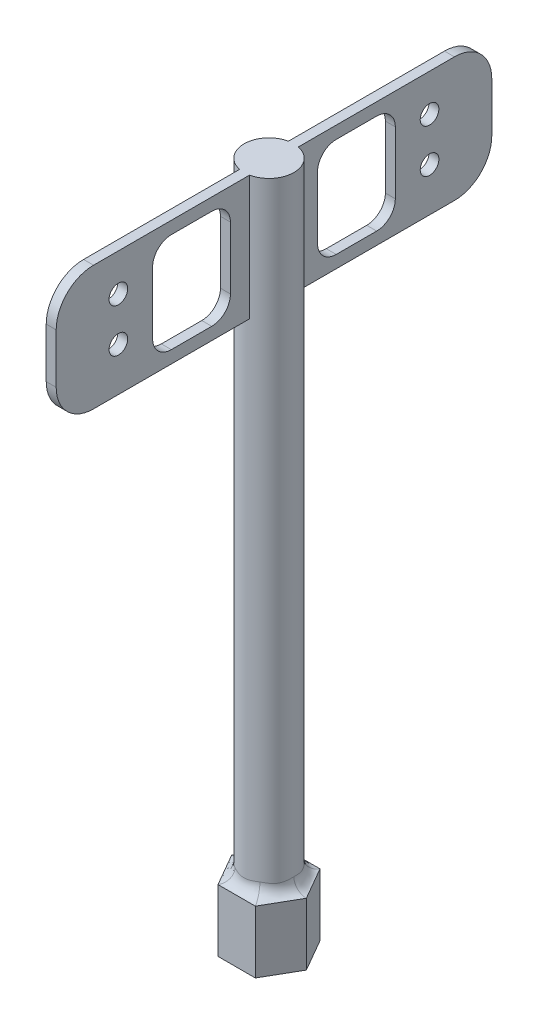
SolidWorks part; units mm, degrees
ref_plane "Front Plane" through (0, 0, 0) normal (0, 0, 1) x (1, 0, 0)
ref_plane "Top Plane" through (0, 0, 0) normal (0, 1, 0) x (1, 0, 0)
ref_plane "Right Plane" through (0, 0, 0) normal (1, 0, 0) x (0, 0, -1)
sketch "Sketch1" plane through (0, 0, 0) normal (0, 1, 0) x (1, 0, 0)
  line L1 (6, 0) -> (3, 5.1962)
  line L2 (3, 5.1962) -> (-3, 5.1962)
  line L3 (-3, 5.1962) -> (-6, 0)
  line L4 (-6, 0) -> (-3, -5.1962)
  line L5 (-3, -5.1962) -> (3, -5.1962)
  line L6 (3, -5.1962) -> (6, 0)
  circle A0 centre (0, 0) radius 5.1962 construction
  dimension "D1" = 6
extrude "Boss-Extrude1" add sketch "Sketch1" along normal blind 10
sketch "Sketch2" plane through (0, 10, 0) normal (0, 1, 0) x (1, 0, 0)
  circle A0 centre (0, 0) radius 4
extrude "Boss-Extrude2" add sketch "Sketch2" along normal blind 100
fillet "Fillet1" radius 2 1 edges at (0, 10, 4)
sketch "Sketch3" plane through (0, 0, 0) normal (0, -1, 0) x (-1, 0, 0)
  circle A0 centre (0, 0) radius 3
extrude "Cut-Extrude1" cut sketch "Sketch3" against normal blind 8
sketch "Sketch4" plane through (0, 110, 0) normal (0, 1, 0) x (1, 0, 0)
  line L1 (-0.8, -35) -> (0.8, -35)
  line L2 (-0.8, -35) -> (-0.8, 35)
  line L3 (-0.8, 35) -> (0.8, 35)
  line L4 (0.8, -35) -> (0.8, 35)
  line L5 (-0.8, -35) -> (0.8, 35) construction
  line L6 (-0.8, 35) -> (0.8, -35) construction
  point P0 (0, 0)
  dimension "D1" = 1.6
  dimension "D2" = 70
extrude "Boss-Extrude3" add sketch "Sketch4" against normal blind 20
sketch "Sketch5" plane through (-0.8, 0, 0) normal (-1, 0, 0) x (0, 0, 1)
  line L0 (0, 0) -> (0, 127.2125) construction
  line L1 (-35, 110) -> (-3.9192, 110) construction
  line L2 (-3.9192, 90) -> (-35, 90) construction
  line L3 (-7, 108) -> (-19.5, 108)
  line L4 (-7, 108) -> (-7, 92)
  line L5 (-7, 92) -> (-19.5, 92)
  line L6 (-19.5, 108) -> (-19.5, 92)
  line L7 (-7, 108) -> (-19.5, 92) construction
  line L8 (-7, 92) -> (-19.5, 108) construction
  line L9 (7, 92) -> (19.5, 92)
  line L10 (7, 108) -> (7, 92)
  line L11 (7, 108) -> (19.5, 108)
  line L12 (19.5, 108) -> (19.5, 92)
  circle A0 centre (-25, 104) radius 1.5
  circle A1 centre (-25, 97) radius 1.5
  circle A2 centre (25, 97) radius 1.5
  circle A3 centre (25, 104) radius 1.5
  point P13 (-13.25, 100)
  dimension "D1" = 25
  dimension "D2" = 7
  dimension "D3" = 6
  dimension "D4" = 7
  dimension "D5" = 2
  dimension "D6" = 2
  dimension "D7" = 12.5
extrude "Cut-Extrude2" cut sketch "Sketch5" against normal blind 20
fillet "Fillet2" radius 6 4 edges at (0, 90, 35) (0, 110, 35) (0, 90, -35) (0, 110, -35)
fillet "Fillet3" radius 3 8 edges at (0, 92, 19.5) (0, 108, 19.5) (0, 108, 7) (0, 92, 7) (0, 108, -7) (0, 92, -7) (0, 92, -19.5) (0, 108, -19.5)
